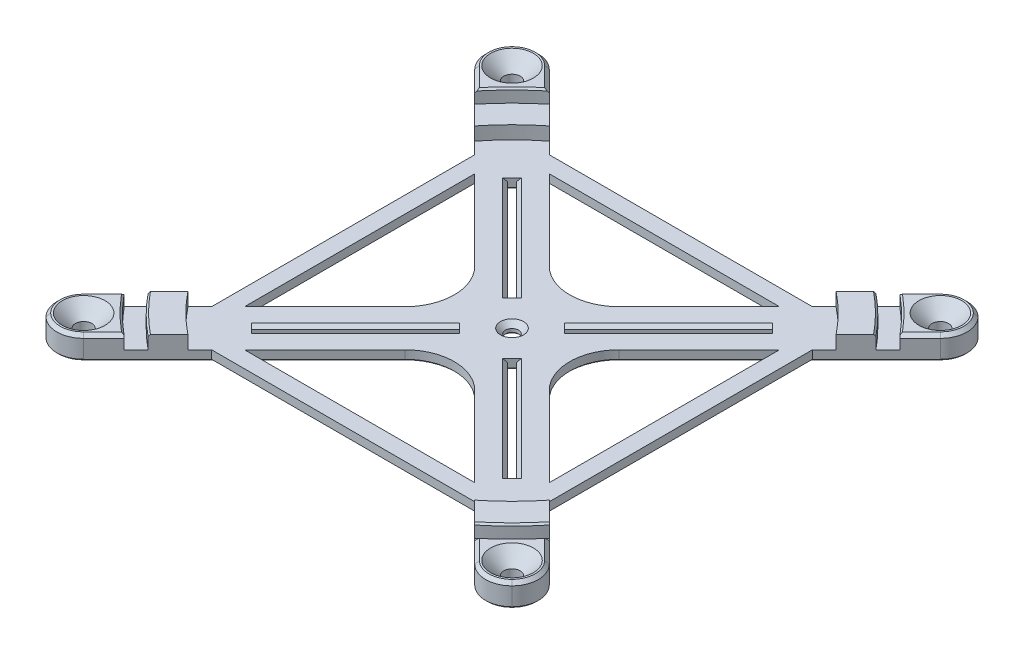
SolidWorks part; units mm, degrees
ref_plane "Спереди" through (0, 0, 0) normal (0, 0, 1) x (1, 0, 0)
ref_plane "Сверху" through (0, 0, 0) normal (0, 1, 0) x (1, 0, 0)
ref_plane "Справа" through (0, 0, 0) normal (1, 0, 0) x (0, 0, -1)
sketch "Эскиз1" plane through (0, 0, 0) normal (0, 1, 0) x (1, 0, 0)
  line L0 (-147.5, 147.5) -> (147.5, -147.5) construction
  line L1 (-147.5, -147.5) -> (147.5, -147.5) construction
  line L2 (-147.5, -147.5) -> (-147.5, 147.5) construction
  line L3 (-147.5, 147.5) -> (147.5, 147.5) construction
  line L4 (147.5, -147.5) -> (147.5, 147.5) construction
  line L5 (0, 147.5) -> (0, -147.5) construction
  line L6 (-147.5, 0) -> (147.5, 0) construction
  line L7 (130.1076, -152.7351) -> (-152.7351, 130.1076)
  line L8 (130.1076, -152.7351) -> (152.7351, -130.1076)
  line L9 (-152.7351, 130.1076) -> (-130.1076, 152.7351)
  line L10 (152.7351, -130.1076) -> (-130.1076, 152.7351)
  circle A0 centre (0, 0) radius 157.5 construction
  point P0 (0, 0)
  point P6 (0, 0)
  dimension "D5" = 32
  dimension "D1" = 295
  dimension "D2" = 295
  dimension "D3" = 400
  dimension "D4" = 45
extrude "Бобышка-Вытянуть1" add sketch "Эскиз1" along normal blind 14
sketch "Эскиз2" plane through (0, 0, 0) normal (0, 1, 0) x (1, 0, 0)
  line L0 (0, 0) -> (189.3234, 0) construction
  line L1 (0, 0) -> (209.4677, 209.4677) construction
  line L2 (-152.7351, -130.1076) -> (130.1076, 152.7351)
  line L3 (-152.7351, -130.1076) -> (-130.1076, -152.7351)
  line L4 (130.1076, 152.7351) -> (152.7351, 130.1076)
  line L5 (-130.1076, -152.7351) -> (152.7351, 130.1076)
  line L6 (-152.7351, -130.1076) -> (152.7351, 130.1076) construction
  line L7 (130.1076, 152.7351) -> (-130.1076, -152.7351) construction
  point P3 (141.4214, 141.4214)
  dimension "D1" = 32
  dimension "D2" = 400
  dimension "D3" = 45
extrude "Бобышка-Вытянуть2" add sketch "Эскиз2" along normal blind 14
fillet "Скругление1" radius 16 8 edges at (-130.1076, 7, -152.7351) (-152.7351, 7, -130.1076) (130.1076, 7, 152.7351) (152.7351, 7, 130.1076) (-130.1076, 7, 152.7351) (-152.7351, 7, 130.1076) (130.1076, 7, -152.7351) (152.7351, 7, -130.1076)
sketch "Эскиз3" plane through (0, 14, 0) normal (0, 1, 0) x (1, 0, 0)
  line L1 (-130, -130) -> (130, -130) construction
  line L2 (-130, -130) -> (-130, 130) construction
  line L3 (-130, 130) -> (130, 130) construction
  line L4 (130, -130) -> (130, 130) construction
  line L5 (0, 130) -> (0, -130) construction
  line L6 (-130, 0) -> (130, 0) construction
  circle A0 centre (-130, -130) radius 5
  circle A1 centre (-130, 130) radius 5
  circle A2 centre (130, 130) radius 5
  circle A3 centre (130, -130) radius 5
  circle A4 centre (0, 0) radius 4
  point P0 (0, 0)
  point P14 (0, 0)
  dimension "D1" = 10
  dimension "D3" = 8
  dimension "D2" = 260
  dimension "D4" = 367.6955
extrude "Вырез-Вытянуть1" cut sketch "Эскиз3" against normal through all
fillet "Скругление2" radius 30 4 edges at (22.6274, 7, 0) (0, 7, 22.6274) (-22.6274, 7, 0) (0, 7, -22.6274)
sketch "Эскиз4" plane through (0, 14, 0) normal (0, 1, 0) x (1, 0, 0)
  circle A0 centre (0, 0) radius 157
  dimension "D1" = 314
extrude "Вырез-Вытянуть-Тонкостенный1" cut sketch "Эскиз4" against normal blind 8 thin thin type one direction wall 10.2
chamfer "Фаска2" distance 1 angle 45 8 edges at (118.2283, 14, 118.2283) (111.0158, 14, 111.0158) (-111.0158, 14, -111.0158) (-118.2283, 14, -118.2283) (118.2283, 14, -118.2283) (111.0158, 14, -111.0158) (-111.0158, 14, 111.0158) (-118.2283, 14, 118.2283)
sketch "Эскиз5" plane through (0, 14, 0) normal (0, 1, 0) x (1, 0, 0)
  circle A0 centre (0, 0) radius 140
  dimension "D1" = 280
extrude "Вырез-Вытянуть2" cut sketch "Эскиз5" against normal blind 8
chamfer "Фаска3" distance 8 angle 45 4 edges at (-130, 14, -125) (130, 14, 135) (130, 14, -125) (-130, 14, 135)
chamfer "Фаска4" distance 2 angle 45 16 edges at (-112.9381, 14, -135.5655) (-130.1076, 14, -146.1076) (-135.5655, 14, -112.9381) (-146.1076, 14, -130.1076) (112.9381, 14, -135.5655) (135.5655, 14, -112.9381) (130.1076, 14, -146.1076) (146.1076, 14, -130.1076) (-135.5655, 14, 112.9381) (-146.1076, 14, 130.1076) (-112.9381, 14, 135.5655) (-130.1076, 14, 146.1076) (112.9381, 14, 135.5655) (130.1076, 14, 146.1076) (135.5655, 14, 112.9381) (146.1076, 14, 130.1076)
chamfer "Фаска5" distance 3 angle 45 1 edges at (0, 6, 4)
sketch "Эскиз8" plane through (0, 6, 0) normal (0, 1, 0) x (1, 0, 0)
  line L0 (0, 149.0517) -> (0, 0) construction
  line L1 (0, 0) -> (158.0685, 158.0685) construction
  line L2 (14.5163, 17.3447) -> (77.659, 80.4874)
  line L3 (14.5163, 17.3447) -> (17.3447, 14.5163)
  line L4 (77.659, 80.4874) -> (80.4874, 77.659)
  line L5 (17.3447, 14.5163) -> (80.4874, 77.659)
  line L6 (14.5163, 17.3447) -> (80.4874, 77.659) construction
  line L7 (77.659, 80.4874) -> (17.3447, 14.5163) construction
  line L8 (17.3447, -14.5163) -> (80.4874, -77.659)
  line L9 (17.3447, -14.5163) -> (14.5163, -17.3447)
  line L10 (14.5163, -17.3447) -> (77.659, -80.4874)
  line L11 (80.4874, -77.659) -> (77.659, -80.4874)
  line L12 (-14.5163, -17.3447) -> (-77.659, -80.4874)
  line L13 (-14.5163, -17.3447) -> (-17.3447, -14.5163)
  line L14 (-17.3447, -14.5163) -> (-80.4874, -77.659)
  line L15 (-77.659, -80.4874) -> (-80.4874, -77.659)
  line L16 (-17.3447, 14.5163) -> (-80.4874, 77.659)
  line L17 (-17.3447, 14.5163) -> (-14.5163, 17.3447)
  line L18 (-14.5163, 17.3447) -> (-77.659, 80.4874)
  line L19 (-80.4874, 77.659) -> (-77.659, 80.4874)
  point P5 (47.5019, 47.5019)
  point P24 (0, 0)
  dimension "D1" = 4
  dimension "D2" = 45
extrude "Вырез-Вытянуть4" cut sketch "Эскиз8" against normal through all
chamfer "Фаска6" distance 2 angle 45 8 edges at (-46.0877, 6, 48.9161) (-48.9161, 6, 46.0877) (48.9161, 6, -46.0877) (46.0877, 6, -48.9161) (46.0877, 6, 48.9161) (48.9161, 6, 46.0877) (-48.9161, 6, -46.0877) (-46.0877, 6, -48.9161)
sketch "Эскиз9" plane through (0, 6, 0) normal (0, 1, 0) x (1, 0, 0)
  line L0 (-86.1627, 102.497) -> (86.4506, 102.497)
  line L1 (-86.1627, 102.497) -> (-86.1627, 92.497)
  line L2 (86.4506, 102.497) -> (86.4506, 92.497)
  line L3 (-86.1627, 92.497) -> (86.4506, 92.497)
  line L4 (-86.1627, 102.497) -> (86.4506, 92.497) construction
  line L5 (86.4506, 102.497) -> (-86.1627, 92.497) construction
  line L6 (102.497, 86.1627) -> (102.497, -86.4506)
  line L7 (102.497, 86.1627) -> (92.497, 86.1627)
  line L8 (92.497, 86.1627) -> (92.497, -86.4506)
  line L9 (102.497, -86.4506) -> (92.497, -86.4506)
  line L10 (86.1627, -102.497) -> (-86.4506, -102.497)
  line L11 (86.1627, -102.497) -> (86.1627, -92.497)
  line L12 (86.1627, -92.497) -> (-86.4506, -92.497)
  line L13 (-86.4506, -102.497) -> (-86.4506, -92.497)
  line L14 (-102.497, -86.1627) -> (-102.497, 86.4506)
  line L15 (-102.497, -86.1627) -> (-92.497, -86.1627)
  line L16 (-92.497, -86.1627) -> (-92.497, 86.4506)
  line L17 (-102.497, 86.4506) -> (-92.497, 86.4506)
  point P1 (0.1439, 97.497)
  point P20 (0, 0)
  dimension "D1" = 10
extrude "Бобышка-Вытянуть3" add sketch "Эскиз9" against normal blind 6
chamfer "Фаска7" distance 1 angle 45 57 edges at (0, 0, 35.0538) (99.3317, 0, 121.9592) (45.5414, 0, 68.1688) (130.1076, 0, 146.1076) (146.1076, 0, 130.1076) (121.9592, 0, 99.3317) (68.1688, 0, 45.5414) (35.0538, 0, 0) (121.9592, 0, -99.3317) (68.1688, 0, -45.5414) (146.1076, 0, -130.1076) (130.1076, 0, -146.1076) (99.3317, 0, -121.9592) (45.5414, 0, -68.1688) (0, 0, -35.0538) (-99.3317, 0, -121.9592) (-45.5414, 0, -68.1688) (-130.1076, 0, -146.1076) (-146.1076, 0, -130.1076) (-68.1688, 0, -45.5414) (-121.9592, 0, -99.3317) (-35.0538, 0, 0) (-68.1688, 0, 45.5414) (-121.9592, 0, 99.3317) (-146.1076, 0, 130.1076) (-130.1076, 0, 146.1076) (-99.3317, 0, 121.9592) (-45.5414, 0, 68.1688) (79.0732, 0, -79.0732) (48.9161, 0, -46.0877) (15.9305, 0, -15.9305) (46.0877, 0, -48.9161) (79.0732, 0, 79.0732) (46.0877, 0, 48.9161) (15.9305, 0, 15.9305) (48.9161, 0, 46.0877) (-79.0732, 0, 79.0732) (-48.9161, 0, 46.0877) (-15.9305, 0, 15.9305) (-46.0877, 0, 48.9161) (-79.0732, 0, -79.0732) (-46.0877, 0, -48.9161) (-15.9305, 0, -15.9305) (-48.9161, 0, -46.0877) (-130, 0, 135) (0, 0, 4) (-130, 0, -125) (130, 0, -125) (130, 0, 135) (0, 0, -92.497) (92.497, 0, 0) (0, 0, 92.497) (0, 0, 102.497) (102.497, 0, 0) (0, 0, -102.497) (-102.497, 0, 0) (-92.497, 0, 0)
